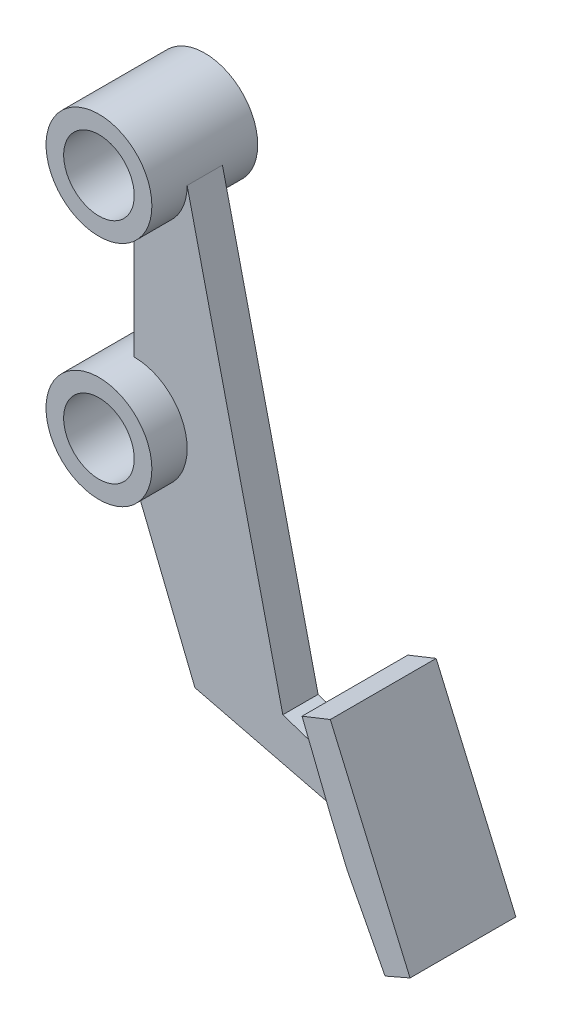
SolidWorks part; units mm, degrees
ref_plane "Płaszczyzna przednia" through (0, 0, 0) normal (0, 0, 1) x (1, 0, 0)
ref_plane "Płaszczyzna górna" through (0, 0, 0) normal (0, 1, 0) x (1, 0, 0)
ref_plane "Płaszczyzna prawa" through (0, 0, 0) normal (1, 0, 0) x (0, 0, -1)
sketch "Szkic1" plane through (0, 0, 0) normal (0, 0, 1) x (1, 0, 0)
  line L0 (0, 15) -> (0, 49.6107)
  line L1 (15, 64.6107) -> (42.1191, -51.7631)
  line L2 (42.1191, -51.7631) -> (65.5793, -59.5114)
  line L3 (65.5793, -59.5114) -> (57.564, -39.386)
  line L4 (57.564, -39.386) -> (65.5793, -36.1938)
  line L5 (65.5793, -36.1938) -> (88.1785, -88.3523)
  line L6 (88.1785, -88.3523) -> (81.0993, -91.4196)
  line L7 (81.0993, -91.4196) -> (70.3211, -70.6829)
  line L8 (70.3211, -70.6829) -> (17.2014, -57.5697)
  line L9 (17.2014, -57.5697) -> (0, -15)
  line L10 (65.5793, -59.5114) -> (70.3211, -70.6829)
  circle A0 centre (0, 0) radius 15
  circle A1 centre (0, 0) radius 10
  circle A2 centre (0, 64.6107) radius 15
  circle A3 centre (0, 64.6107) radius 10
  dimension "D1" = 30
  dimension "D2" = 20
  dimension "D3" = 30
  dimension "D4" = 20
extrude "Dodanie-wyciągnięcie1" add sketch "Szkic1" along normal mid plane 10 contours A2 L0 A0 L9 L8 L7 L6 L5 L4 L3 L2 L1 region at (22.6638, -12.8398, 0)
extrude "Dodanie-wyciągnięcie2" add sketch "Szkic1<3>" along normal mid plane 30 contours A0 A1 | A3 | L3 L10 L7 L6 L5 L4 | A2 region at (10.3066, 10.3066, 0) region at (72.6075, -63.5918, 0) region at (0, 64.6107, 0)
sketch "Szkic1<3>" plane through (0, 0, 0) normal (0, 0, 1) x (1, 0, 0) same geometry as "Szkic1"
